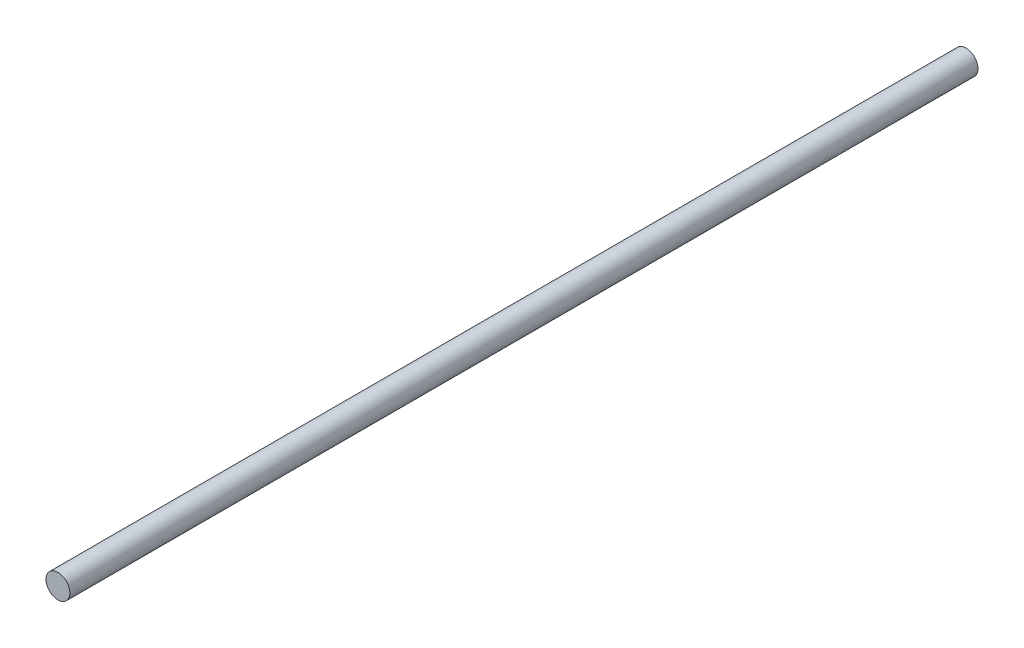
SolidWorks part; units mm, degrees
ref_plane "Front Plane" through (0, 0, 0) normal (0, 0, 1) x (1, 0, 0)
ref_plane "Top Plane" through (0, 0, 0) normal (0, 1, 0) x (1, 0, 0)
ref_plane "Right Plane" through (0, 0, 0) normal (1, 0, 0) x (0, 0, -1)
sketch "base" plane through (0, 0, 0) normal (0, 0, 1) x (1, 0, 0)
  circle A0 centre (0, 0) radius 50
  arc A4 (10, 48.9898) -> (-10, 48.9898) centre (0, 0) ccw construction
extrude "Boss-Extrude1" add sketch "base" along normal blind 2800 and the other way blind 1000
